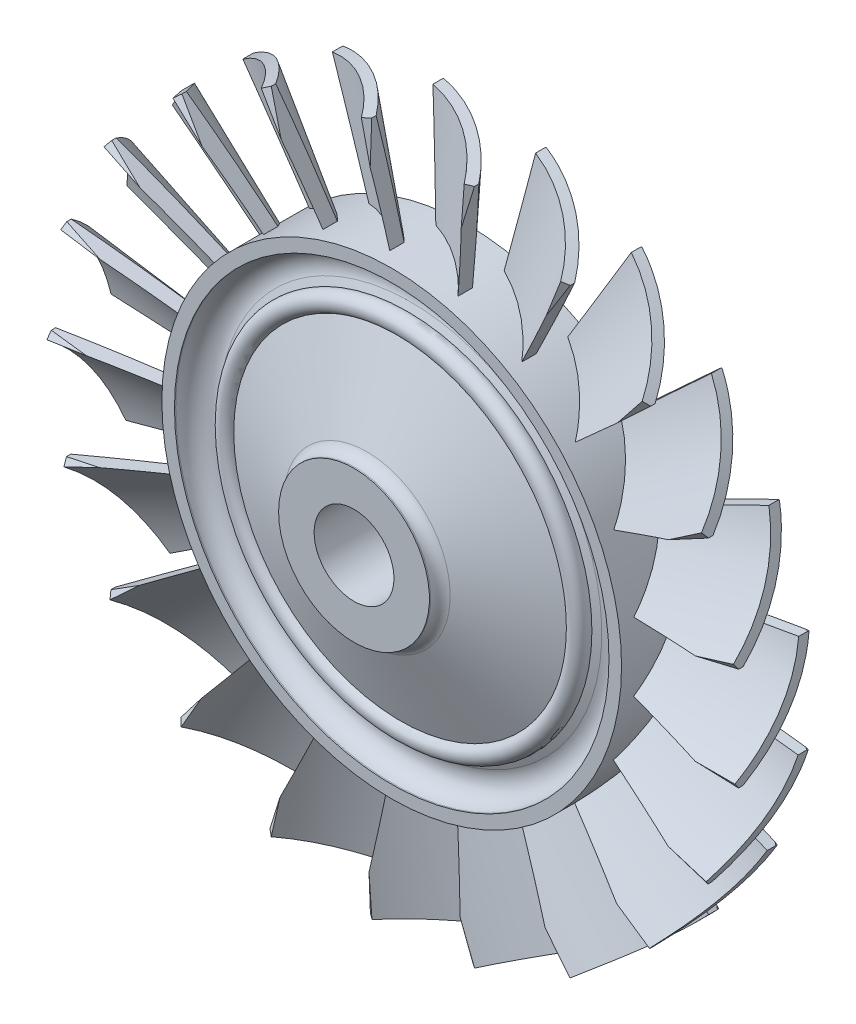
SolidWorks part; units mm, degrees
material "Nickel"
ref_plane "Front Plane" through (0, 0, 0) normal (0, 0, 1) x (1, 0, 0)
ref_plane "Top Plane" through (0, 0, 0) normal (0, 1, 0) x (1, 0, 0)
ref_plane "Right Plane" through (0, 0, 0) normal (1, 0, 0) x (0, 0, -1)
sketch "Sketch1" plane through (0, 0, 0) normal (1, 0, 0) x (0, 0, -1)
  line L0 (0, 0) -> (-39.1763, 0) construction
  line L1 (6, 3.175) -> (-6, 3.175)
  line L2 (0, 84.6785) -> (0, 0) construction
  line L3 (-6, 3.175) -> (-6, 6)
  line L4 (-6, 6) -> (-5.9, 6)
  line L5 (-4.9724, 6.6264) -> (-2.2952, 13.2743)
  line L6 (-2.9, 17.288) -> (-3, 17.288)
  line L7 (-3, 17.288) -> (-3, 18.288)
  line L8 (-3, 18.288) -> (3, 18.288)
  line L9 (-1.7349, 14.6657) -> (-1.5086, 15.2277)
  line L10 (1.7349, 14.6657) -> (1.5086, 15.2277)
  line L11 (3, 17.288) -> (3, 18.288)
  line L12 (2.9, 17.288) -> (3, 17.288)
  line L13 (4.9724, 6.6264) -> (2.2952, 13.2743)
  line L14 (6, 6) -> (5.9, 6)
  line L15 (6, 3.175) -> (6, 6)
  arc A0 (-5.9, 6) -> (-4.9724, 6.6264) centre (-5.9, 7) ccw
  arc A1 (-1.5086, 15.2277) -> (-2.9, 17.288) centre (-2.9, 15.788) ccw
  arc A2 (-1.7349, 14.6657) -> (-2.2952, 13.2743) centre (-2.0151, 13.97) ccw
  arc A3 (1.7349, 14.6657) -> (2.2952, 13.2743) centre (2.0151, 13.97) cw
  arc A4 (1.5086, 15.2277) -> (2.9, 17.288) centre (2.9, 15.788) cw
  arc A5 (5.9, 6) -> (4.9724, 6.6264) centre (5.9, 7) cw
  point P29 (0, 18.288)
  point P32 (0, 3.175)
  dimension "D5" = 1
  dimension "D6" = 1.5
  dimension "D12" = 1.5
  dimension "D1" = 12
  dimension "D2" = 3
  dimension "D3" = 6.35
  dimension "D4" = 12
  dimension "D7" = 36.576
  dimension "D8" = 1
  dimension "D9" = 0.1
  dimension "D10" = 0.1
  dimension "D11" = 27.94
revolve "Revolve1" add sketch "Sketch1" angle 360 about L0
ref_plane "Plane1" through (17.3, 0, 0) normal (1, 0, 0) x (0, 0, -1)
sketch "Sketch2" plane through (17.3, 0, 0) normal (1, 0, 0) x (0, 0, -1)
  line L2 (0, 0) -> (-12.7641, 0) construction
  line L5 (-3, 18.288) -> (-3, -18.288) construction
  line L6 (3, -18.288) -> (3, 18.288) construction
  arc A0 (-2.7, -4) -> (2.6, 4) centre (-11.0142, 7.2638) ccw
  dimension "D3" = 14
  dimension "D1" = 4
  dimension "D2" = 4
  dimension "D4" = 0.3
  dimension "D5" = 0.4
extrude "fin" add sketch "Sketch2" along normal blind 11 separate body thin thin type mid plane wall 0.8
ref_axis "Axis1" through (0, 0, 6) along (0, 0, -1)
sketch "Sketch4" plane through (0, 0, 6) normal (0, 0, 1) x (1, 0, 0)
  line L0 (18.0997, 2.6179) -> (28.3, 4.0933)
  line L1 (28.3, 4.0933) -> (28.3, -4.3218)
  line L2 (28.3, -4.3218) -> (18.0784, -2.7608)
  circle A0 centre (0, 0) radius 18.288 construction
  arc A1 (18.0997, 2.6179) -> (18.0784, -2.7608) centre (0, 0) ccw
extrude "Cut-Extrude2" cut sketch "Sketch4" against normal blind 10 flip side to cut
pattern_circular "CirPattern1" count 21 over 360 about axis through (0, 0, 6) along (0, 0, -1) of bodies 105
sketch "Sketch3" plane through (0, 0, 6) normal (0, 0, 1) x (1, 0, 0)
  circle A0 centre (0, 0) radius 27.5
  dimension "D1" = 55
extrude "Cut-Extrude1" cut sketch "Sketch3" against normal through all flip side to cut
combine bodies "Combine1" operation type add bodies to combine 133 134 135 136 137 138 101 139 104 140 126 141 127 142 128 143 129 144 145 130 131 132
